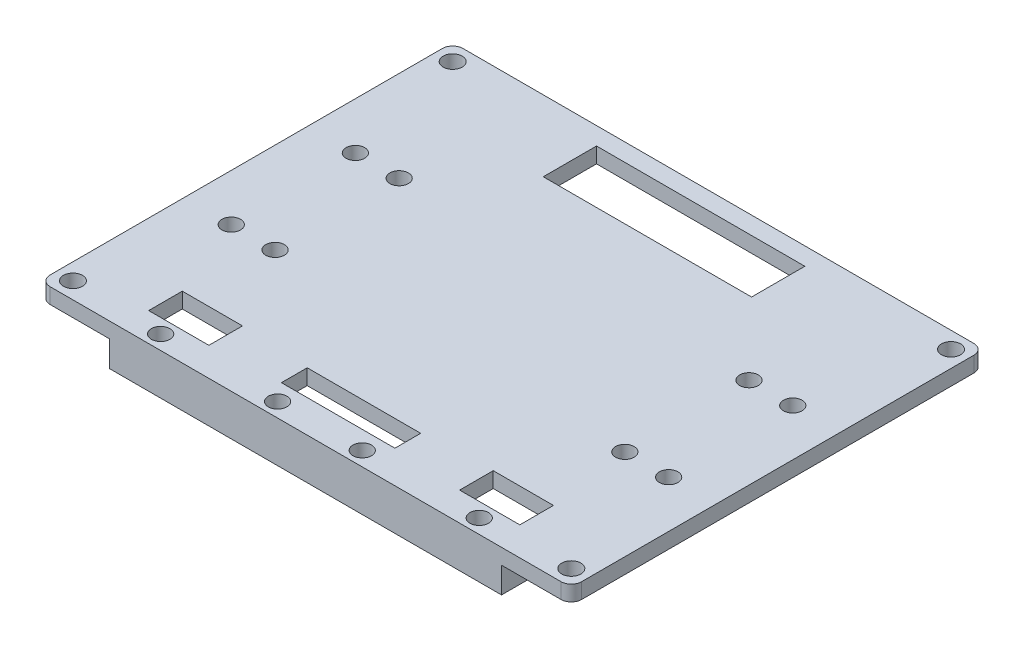
SolidWorks part; units mm, degrees
ref_plane "前视基准面" through (0, 0, 0) normal (0, 0, 1) x (1, 0, 0)
ref_plane "上视基准面" through (0, 0, 0) normal (0, 1, 0) x (1, 0, 0)
ref_plane "右视基准面" through (0, 0, 0) normal (1, 0, 0) x (0, 0, -1)
sketch "草图1" plane through (0, 0, 0) normal (0, 1, 0) x (1, 0, 0)
  line L0 (-51.5, 40) -> (-48.2968, 36.7968) construction
  line L1 (49.5, -40) -> (-49.5, -40)
  line L2 (51.5, -38) -> (51.5, 38)
  line L3 (49.5, 40) -> (-49.5, 40)
  line L4 (-51.5, -38) -> (-51.5, 38)
  line L5 (51.5, -40) -> (-51.5, 40) construction
  line L6 (51.5, 40) -> (-51.5, -40) construction
  line L7 (20.1874, 26.2491) -> (-20.1874, 26.2491)
  line L8 (20.1874, 26.2491) -> (20.1874, 36.5704)
  line L9 (20.1874, 36.5704) -> (-20.1874, 36.5704)
  line L10 (-20.1874, 26.2491) -> (-20.1874, 36.5704)
  line L11 (20.1874, 26.2491) -> (-20.1874, 36.5704) construction
  line L12 (20.1874, 36.5704) -> (-20.1874, 26.2491) construction
  line L13 (0, 31.4098) -> (0, -40) construction
  line L14 (51.5, 0) -> (-51.5, 0)
  line L16 (11, -33.6959) -> (-11, -33.6959)
  line L17 (11, -33.6959) -> (11, -28.6959)
  line L18 (11, -28.6959) -> (-11, -28.6959)
  line L19 (-11, -33.6959) -> (-11, -28.6959)
  line L20 (11, -33.6959) -> (-11, -28.6959) construction
  line L21 (11, -28.6959) -> (-11, -33.6959) construction
  line L26 (24.3014, -27.9372) -> (35.9691, -27.9372)
  line L27 (-24.3014, -34.4545) -> (-35.9691, -34.4545)
  line L31 (-24.3014, -34.4545) -> (-24.3014, -27.9372)
  line L32 (-24.3014, -27.9372) -> (-35.9691, -27.9372)
  line L33 (-35.9691, -34.4545) -> (-35.9691, -27.9372)
  line L34 (-24.3014, -34.4545) -> (-35.9691, -27.9372) construction
  line L35 (-24.3014, -27.9372) -> (-35.9691, -34.4545) construction
  line L36 (35.9691, -34.4545) -> (35.9691, -27.9372)
  line L37 (24.3014, -34.4545) -> (35.9691, -34.4545)
  line L38 (24.3014, -34.4545) -> (24.3014, -27.9372)
  line L39 (-48.2968, 36.7968) -> (-48.2968, -36.7968) construction
  line L47 (-38.1468, 18.3) -> (-38.1468, -18.3) construction
  line L48 (-38.1468, 18.3) -> (-38.1468, 12.03)
  line L49 (-33.9018, 12.03) -> (-42.3918, 12.03)
  circle A0 centre (-48.2968, 36.7968) radius 1.85
  circle A1 centre (48.2968, 36.7968) radius 1.85
  circle A2 centre (48.2968, -36.7968) radius 1.85
  circle A3 centre (-48.2968, -36.7968) radius 1.85
  arc A4 (-49.5, -40) -> (-51.5, -38) centre (-49.5, -38) cw
  arc A5 (49.5, -40) -> (51.5, -38) centre (49.5, -38) ccw
  arc A6 (51.5, 38) -> (49.5, 40) centre (49.5, 38) ccw
  arc A7 (-49.5, 40) -> (-51.5, 38) centre (-49.5, 38) ccw
  circle A8 centre (-42.3918, 12.03) radius 1.8
  circle A9 centre (-33.9018, 12.03) radius 1.8
  circle A10 centre (-33.9018, -12.03) radius 1.8
  circle A11 centre (-42.3918, -12.03) radius 1.8
  circle A12 centre (33.9018, -12.03) radius 1.8
  circle A13 centre (42.3918, -12.03) radius 1.8
  circle A14 centre (33.9018, 12.03) radius 1.8
  circle A15 centre (42.3918, 12.03) radius 1.8
  point P0 (0, 0)
  point P6 (0, 31.4098)
  point P18 (0, 0)
  point P36 (0, -31.1959)
  point P41 (-69.6672, -54.1104)
  point P42 (-30.1353, -31.1959)
  point P54 (-48.2968, 0)
  point P62 (-38.1468, 12.03)
  dimension "D4" = 2
  dimension "D1" = 103
  dimension "D2" = 80
  dimension "D3" = 45
extrude "凸台-拉伸1" add sketch "草图1" along normal blind 3 contours L3 A7 L4 L14 L2 A6 L7 L10 L9 L8 A0 A1 | L1 A5 L2 L14 L4 A4 A3 A2 region at (0, 0, 19.2081) region at (0, 0, -18.6742)
ref_plane "基准面1" through (0, 3, 0) normal (0, 1, 0) x (1, 0, 0)
sketch "草图2" plane through (0, 3, 0) normal (0, 1, 0) x (1, 0, 0)
  line L0 (49.5, -40) -> (-49.5, -40) construction
  line L1 (-37.9691, -34.4545) -> (37.9691, -34.4545)
  line L2 (-37.9691, -34.4545) -> (-37.9691, -40)
  line L3 (-37.9691, -40) -> (37.9691, -40)
  line L4 (37.9691, -34.4545) -> (37.9691, -40)
  line L5 (0, -34.4545) -> (0, -40) construction
  point P13 (0, -37.2273)
  point P16 (0, -37.2273)
  dimension "D1" = 2
  dimension "D2" = 2
extrude "凸台-拉伸2" add sketch "草图2" against normal blind 8
ref_plane "基准面2" through (0, -5, 0) normal (0, -1, 0) x (-1, 0, 0)
sketch "草图3" plane through (0, -5, 0) normal (0, -1, 0) x (-1, 0, 0)
  line L0 (0, -40) -> (0, -34.4545) construction
  line L1 (37.9691, -40) -> (-37.9691, -40) construction
  line L2 (-37.9691, -34.4545) -> (37.9691, -34.4545) construction
  line L3 (15, -37.2273) -> (-15, -37.2273)
  line L4 (10, -37.2273) -> (-10, -37.2273)
  circle A0 centre (-8.2, -37.2273) radius 1.8
  circle A1 centre (8.2, -37.2273) radius 1.8
  circle A2 centre (-30.8751, -37.2273) radius 1.8
  circle A3 centre (30.8751, -37.2273) radius 1.8
  point P9 (0, -37.2273)
  point P12 (0, -37.2273)
  dimension "D1" = 20
extrude "切除-拉伸1" cut sketch "草图3" against normal blind 15 contours A3 | L3 A1 | L3 A1 | L4 A0 | A2 | A0 region at (-8.2, -5, 36.4633) region at (-8.2, -5, 37.9912) region at (8.2, -5, 36.4633) region at (30.8751, -5, 37.2273) region at (-30.8751, -5, 37.2273)
